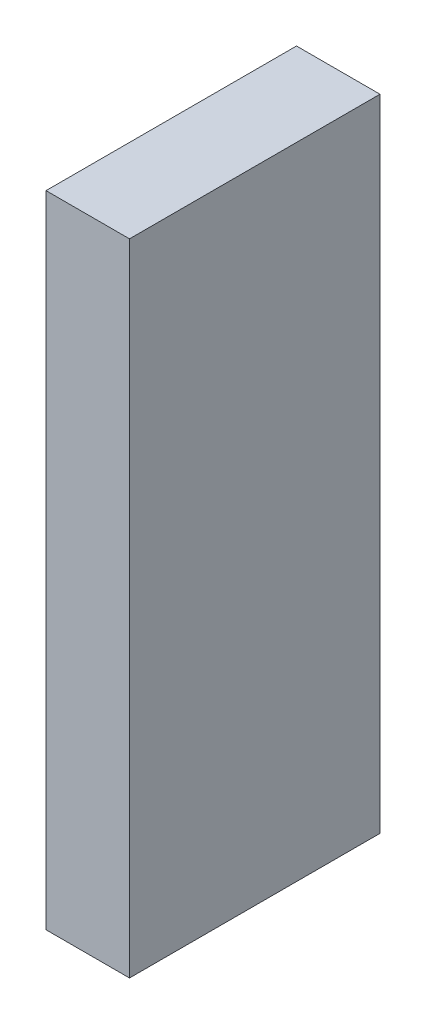
SolidWorks part; units mm, degrees
ref_plane "Front Plane" through (0, 0, 0) normal (0, 0, 1) x (1, 0, 0)
ref_plane "Top Plane" through (0, 0, 0) normal (0, 1, 0) x (1, 0, 0)
ref_plane "Right Plane" through (0, 0, 0) normal (1, 0, 0) x (0, 0, -1)
sketch "Sketch1" plane through (0, 0, 0) normal (0, 1, 0) x (1, 0, 0)
  line L1 (-15, 45) -> (15, 45)
  line L2 (-15, 45) -> (-15, -45)
  line L3 (-15, -45) -> (15, -45)
  line L4 (15, 45) -> (15, -45)
  line L5 (-15, 45) -> (15, -45) construction
  line L6 (-15, -45) -> (15, 45) construction
  point P0 (0, 0)
  dimension "D1" = 30
  dimension "D2" = 90
extrude "Boss-Extrude1" add sketch "Sketch1" along normal mid plane 230
